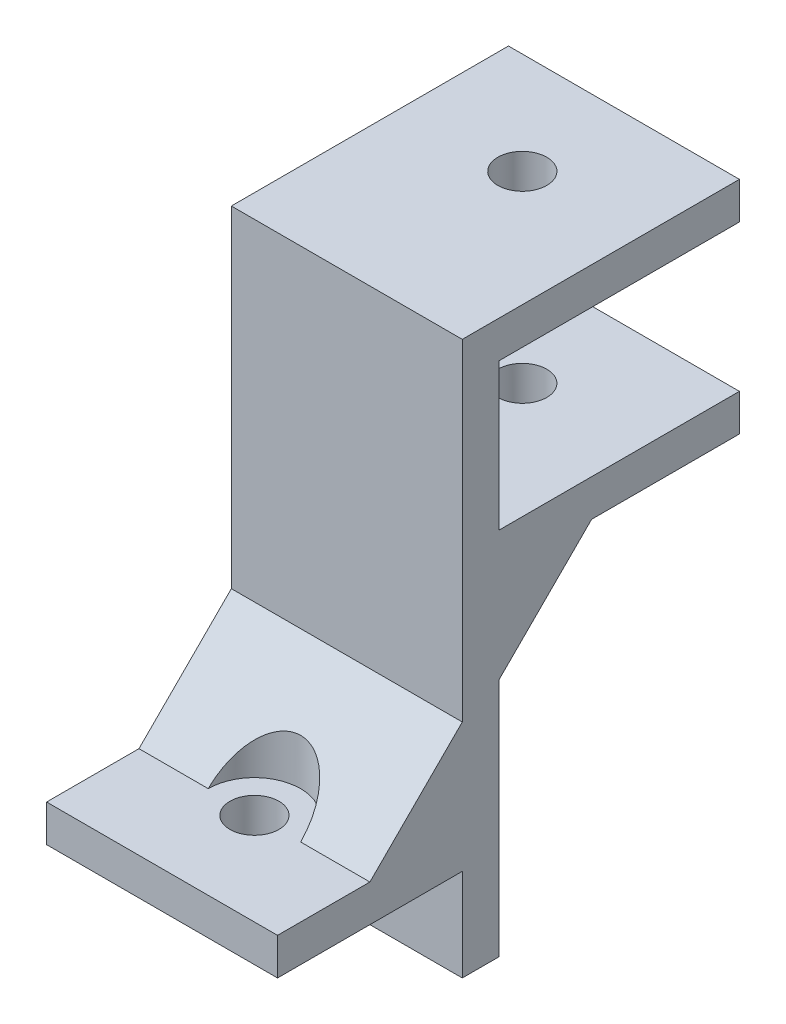
SolidWorks part; units mm, degrees
ref_plane "Front Plane" through (0, 0, 0) normal (0, 0, 1) x (1, 0, 0)
ref_plane "Top Plane" through (0, 0, 0) normal (0, 1, 0) x (1, 0, 0)
ref_plane "Right Plane" through (0, 0, 0) normal (1, 0, 0) x (0, 0, -1)
sketch "Sketch1" plane through (0, 0, 0) normal (1, 0, 0) x (0, 0, -1)
  line L0 (0, 0) -> (0, 10)
  line L1 (4, 40) -> (30, 40)
  line L7 (0, 59.875) -> (30, 59.875)
  line L8 (30, 59.875) -> (30, 55.875)
  line L9 (30, 55.875) -> (4, 55.875)
  line L10 (4, 55.875) -> (4, 40)
  line L11 (0, 14) -> (-20, 14)
  line L12 (-20, 14) -> (-20, 10)
  line L13 (-20, 10) -> (0, 10)
  line L14 (0, 14) -> (0, 59.875)
  line L15 (30, 40) -> (30, 36)
  line L16 (30, 36) -> (4, 36)
  line L17 (4, 36) -> (4, 0)
  line L18 (4, 0) -> (0, 0)
  dimension "D1" = 20
  dimension "D2" = 30
  dimension "D3" = 4
  dimension "D4" = 4
  dimension "D5" = 15.875
  dimension "D6" = 4
  dimension "D7" = 30
  dimension "D8" = 10
  dimension "D9" = 4
  dimension "D10" = 4
extrude "Boss-Extrude1" add sketch "Sketch1" along normal blind 25
sketch "Sketch2" plane through (0, 14, 0) normal (0, 1, 0) x (1, 0, 0)
  line L0 (12.5, 0) -> (12.5, -20) construction
  line L1 (25, 0) -> (0, 0) construction
  line L2 (25, -20) -> (0, -20) construction
  circle A0 centre (12.5, -10) radius 2.65
  dimension "D1" = 5.3
  dimension "D2" = 10
extrude "Cut-Extrude1" cut sketch "Sketch2" against normal blind 6 and the other way blind 6
sketch "Sketch3" plane through (0, 59.875, 0) normal (0, 1, 0) x (1, 0, 0)
  line L0 (12.5, 30) -> (12.5, 0) construction
  line L1 (25, 30) -> (0, 30) construction
  line L2 (25, 0) -> (0, 0) construction
  circle A0 centre (12.5, 19) radius 2.65
  dimension "D1" = 5.3
  dimension "D2" = 19
extrude "Cut-Extrude2" cut sketch "Sketch3" against normal through all
chamfer "Chamfer1" distance 10 angle 45 1 edges at (12.5, 14, 0)
sketch "Sketch4" plane through (0, 14, 0) normal (0, 1, 0) x (1, 0, 0)
  circle A0 centre (12.5, -10) radius 5
  dimension "D1" = 10
extrude "Cut-Extrude4" cut sketch "Sketch4" along normal blind 6
chamfer "Chamfer2" distance 10 angle 45 1 edges at (12.5, 36, -4)
